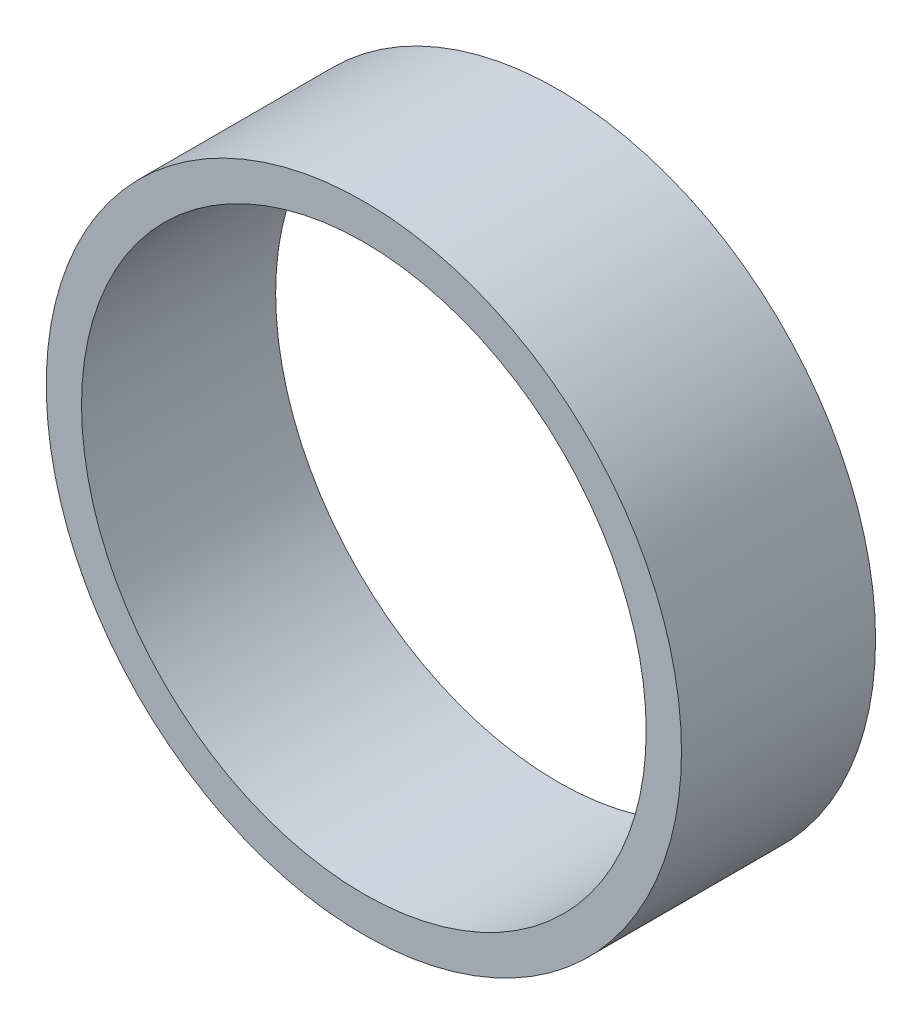
SolidWorks part; units mm, degrees
ref_plane "Front" through (0, 0, 0) normal (0, 0, 1) x (1, 0, 0)
ref_plane "Top" through (0, 0, 0) normal (0, 1, 0) x (1, 0, 0)
ref_plane "Right" through (0, 0, 0) normal (1, 0, 0) x (0, 0, -1)
sketch "Эскиз1" plane through (0, 0, 0) normal (0, 0, 1) x (1, 0, 0)
  circle A0 centre (0, 0) radius 8
  circle A1 centre (0, 0) radius 9
extrude "Бобышка-Вытянуть1" add sketch "Эскиз1" along normal blind 5.5
